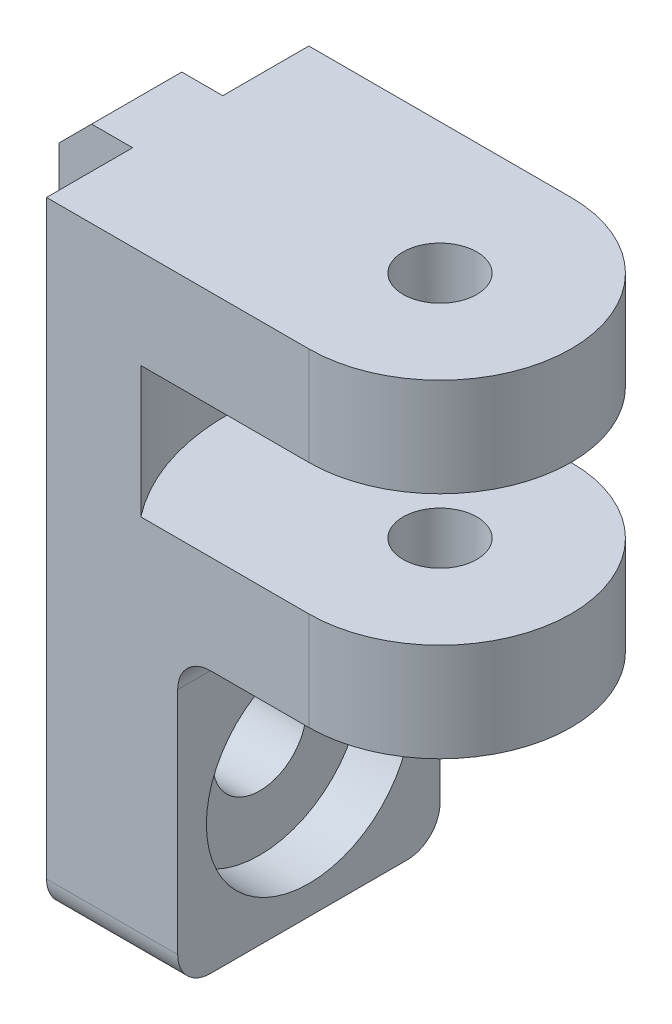
SolidWorks part; units mm, degrees
ref_plane "Front Plane" through (0, 0, 0) normal (0, 0, 1) x (1, 0, 0)
ref_plane "Top Plane" through (0, 0, 0) normal (0, 1, 0) x (1, 0, 0)
ref_plane "Right Plane" through (0, 0, 0) normal (1, 0, 0) x (0, 0, -1)
sketch "Sketch1" plane through (0, 0, 0) normal (1, 0, 0) x (0, 0, -1)
  line L0 (-32.8466, 35.9115) -> (-32.8466, -2.0885)
  line L1 (-48.8466, 35.9115) -> (-32.8466, 35.9115)
  line L5 (-32.8466, -2.0885) -> (-48.8466, -2.0885)
  line L6 (-48.8466, -2.0885) -> (-48.8466, 35.9115)
  dimension "D9" = 16
  dimension "D10" = 38
extrude "Boss-Extrude1" add sketch "Sketch1" along normal blind 8
sketch "Sketch2" plane through (0, 0, 0) normal (-1, 0, 0) x (0, 0, 1)
  line L0 (40.8466, 5.9115) -> (40.8466, 24.9115) construction
  line L1 (48.8466, 35.9115) -> (48.8466, -2.0885) construction
  line L2 (32.8466, 35.9115) -> (48.8466, 35.9115) construction
  line L3 (38.0966, 35.9115) -> (43.5966, 35.9115)
  line L4 (38.0966, 35.9115) -> (38.0966, 13.9115)
  line L5 (38.0966, 13.9115) -> (43.5966, 13.9115)
  line L6 (43.5966, 35.9115) -> (43.5966, 13.9115)
  line L7 (38.0966, 35.9115) -> (43.5966, 13.9115) construction
  line L8 (38.0966, 13.9115) -> (43.5966, 35.9115) construction
  point P5 (40.8466, 24.9115)
  dimension "D1" = 5.5
  dimension "D3" = 8
extrude "Boss-Extrude2" add sketch "Sketch2" along normal blind 4.5
sketch "Sketch6" plane through (0, 35.9115, 0) normal (0, -1, 0) x (1, 0, 0)
  line L0 (8, 48.8466) -> (16, 48.8466)
  line L2 (16, 32.8466) -> (8, 32.8466)
  line L3 (8, 32.8466) -> (8, 48.8466)
  arc A0 (16, 32.8466) -> (16, 48.8466) centre (16, 40.8466) ccw
  circle A1 centre (16, 40.8466) radius 2.25
  dimension "D2" = 4.5
  dimension "D1" = 8
extrude "Boss-Extrude3" add sketch "Sketch6" along normal blind 20
fillet "Fillet6" radius 2 1 edges at (8, 15.9115, 40.8466)
chamfer "Chamfer1" distance 2 angle 45 2 edges at (-4.5, 13.9115, 40.8466) (-4.5, 35.9115, 40.8466)
sketch "Sketch7" plane through (8, 0, 0) normal (1, 0, 0) x (0, 0, -1)
  line L0 (-48.8466, -2.0885) -> (-32.8466, -2.0885) construction
  line L1 (-32.8466, -2.0885) -> (-32.8466, 13.9115) construction
  circle A0 centre (-40.8466, 5.9115) radius 2.85
  dimension "D1" = 8
  dimension "D3" = 5.7
  dimension "D2" = 8
extrude "Cut-Extrude1" cut sketch "Sketch7" against normal blind 10
sketch "Sketch8" plane through (8, 0, 0) normal (1, 0, 0) x (0, 0, -1)
  circle A0 centre (-40.8466, 5.9115) radius 6.25
  dimension "D1" = 12.5
extrude "Cut-Extrude2" cut sketch "Sketch8" against normal blind 3
sketch "Sketch9" plane through (0, 35.9115, 0) normal (0, 1, 0) x (1, 0, 0)
  circle A0 centre (16, -40.8466) radius 13
  arc A1 (16, -48.8466) -> (16, -32.8466) centre (16, -40.8466) ccw construction
  dimension "D1" = 5
extrude "Cut-Extrude3" cut sketch "Sketch9" against normal mid plane 8 from offset 10 offset against normal yes
fillet "Fillet7" radius 2 2 edges at (4, -2.0885, 32.8466) (4, -2.0885, 48.8466)
